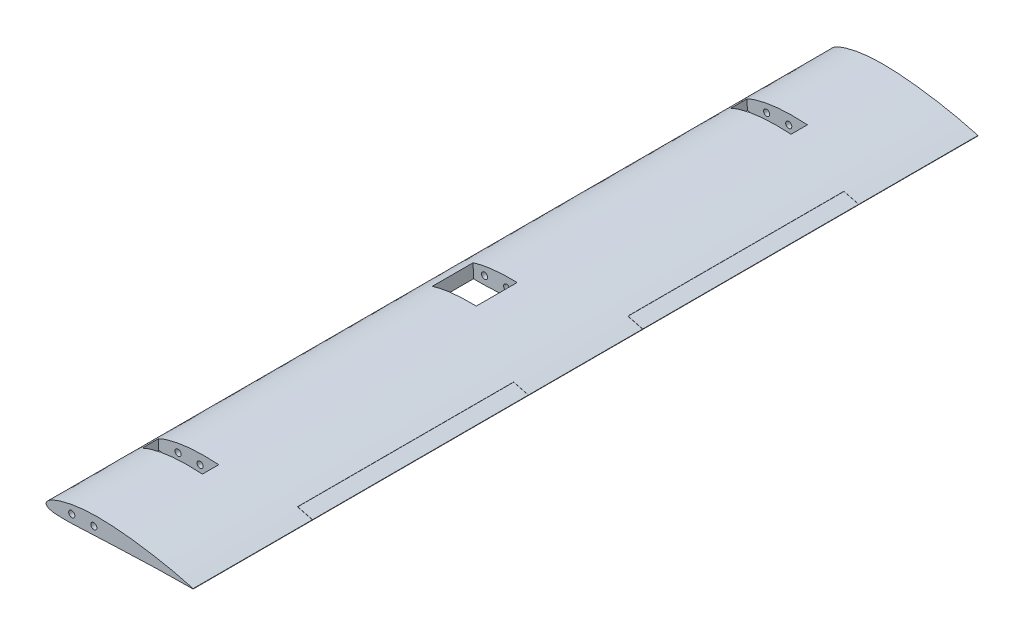
SolidWorks part; units mm, degrees
material "Styrofoam Core 20"
ref_plane "Front Plane" through (0, 0, 0) normal (0, 0, 1) x (1, 0, 0)
ref_plane "Top Plane" through (0, 0, 0) normal (0, 1, 0) x (1, 0, 0)
ref_plane "Right Plane" through (0, 0, 0) normal (1, 0, 0) x (0, 0, -1)
other "Center of Mass"
curve "NACA 4412"
  spline degree 3 poles (25.4, 0.033, 0) (24.9771, 0.1481, 0) (24.1334, 0.3778, 0) (22.4431, 0.7955, 0) (20.3293, 1.2569, 0) (17.7869, 1.7118, 0) (15.2464, 2.0846, 0) (12.7045, 2.3505, 0) (10.1628, 2.5164, 0) (8.041, 2.5181, 0) (6.3469, 2.4009, 0) (5.0745, 2.2465, 0) (3.7995, 2.0188, 0) (2.7428, 1.745, 0) (1.8961, 1.4685, 0) (1.2577, 1.2074, 0) (0.7129, 0.9251, 0) (0.2401, 0.5874, 0) (-0.1715, 0.0442, 0) (0.2727, -0.3711, 0) (0.7261, -0.5342, 0) (1.266, -0.6443, 0) (1.9036, -0.7002, 0) (2.7513, -0.7398, 0) (3.8103, -0.7368, 0) (5.0806, -0.7013, 0) (6.3499, -0.6336, 0) (8.0433, -0.5544, 0) (10.1596, -0.4528, 0) (12.7001, -0.3574, 0) (15.2397, -0.2514, 0) (17.7796, -0.1611, 0) (20.3198, -0.0947, 0) (22.4366, -0.061, 0) (24.13, -0.0388, 0) (24.9767, -0.035, 0) (25.4, -0.033, 0) knots 0 0 0 0 0.025305 0.050488 0.10052 0.150191 0.199587 0.24874 0.297716 0.346601 0.371103 0.395726 0.42057 0.445825 0.458702 0.47192 0.485786 0.493461 0.506863 0.516148 0.522766 0.535269 0.547551 0.559786 0.584229 0.608681 0.633151 0.657622 0.706558 0.755482 0.804406 0.85332 0.902221 0.951113 0.975557 1 1 1 1
sketch "Sketch2" plane through (0, 0, 0) normal (0, 0, 1) x (1, 0, 0)
  line L1 (228.6, 12.387) -> (228.6, 11.7928)
  line L2 (40.005, 31.2493) -> (40.005, 5.6305) construction
  line L3 (68.58, 34.393) -> (68.58, 6.961) construction
  line L4 (74.2832, 19.3375) -> (40.005, 18.4399) construction
  line L5 (0, 0) -> (0, 12.7) construction
  line L6 (40.005, 18.4399) -> (60.8151, 18.4399) construction
  line L7 (68.58, 34.393) -> (228.6056, 20.677) construction
  line L8 (228.6056, 20.677) -> (68.58, 6.961) construction
  line L9 (68.58, 20.677) -> (228.6056, 20.677) construction
  line L11 (59.9523, -93.7228) -> (219.9779, -107.4388)
  line L12 (219.9779, -107.4388) -> (59.9523, -121.1548)
  line L14 (61.264, -169.3292) -> (106.984, -169.3292)
  line L16 (106.984, -141.8972) -> (61.264, -141.8972)
  line L17 (106.984, -141.8972) -> (221.2897, -155.6132)
  line L18 (106.984, -169.3292) -> (221.2897, -155.6132)
  circle A0 centre (40.005, 18.4399) radius 4.7625
  circle A1 centre (74.2832, 19.3375) radius 4.7625
  circle A2 centre (30.4326, -102.8904) radius 4.7625
  circle A3 centre (47.3544, -108.3106) radius 4.7625
  circle A4 centre (31.7443, -151.0648) radius 4.7625
  circle A5 centre (48.6661, -156.485) radius 4.7625
  ellipse E0 centre (68.58, 20.677) end of major axis (0, 20.677) minor radius 13.716 (68.58, 34.393) -> (68.58, 6.961) ccw construction
  ellipse E1 centre (59.9523, -107.4388) end of major axis (128.5323, -107.4388) minor radius 13.716 (59.9523, -93.7228) -> (59.9523, -121.1548) ccw
  ellipse E2 centre (61.264, -155.6132) end of major axis (129.844, -155.6132) minor radius 13.716 (61.264, -141.8972) -> (61.264, -169.3292) ccw
  spline S1 degree 3 poles (228.6, 12.387) (224.795, 13.4228) (217.2034, 15.4895) (201.9951, 19.2471) (182.9766, 23.3988) (160.101, 27.4914) (137.2432, 30.846) (114.3726, 33.2389) (91.504, 34.7313) (72.413, 34.7464) (57.1699, 33.6918) (45.7222, 32.3028) (34.2497, 30.2543) (24.7428, 27.7908) (17.1245, 25.3027) (11.3801, 22.9538) (6.4787, 20.4136) (2.2242, 17.375) (-1.4793, 12.488) (2.5182, 8.7506) (6.5972, 7.2835) (11.455, 6.2932) (17.1921, 5.7898) (24.819, 5.4335) (34.3469, 5.4602) (45.7763, 5.78) (57.1976, 6.389) (72.4334, 7.1015) (91.4748, 8.016) (114.3327, 8.8746) (137.1833, 9.8281) (160.036, 10.6401) (182.8906, 11.2375) (201.9369, 11.5408) (217.1729, 11.7405) (224.791, 11.7754) (228.6, 11.7928) knots 0 0 0 0 0.025305 0.050488 0.10052 0.150191 0.199587 0.24874 0.297716 0.346601 0.371103 0.395726 0.42057 0.445825 0.458702 0.47192 0.485786 0.493461 0.506863 0.516148 0.522766 0.535269 0.547551 0.559786 0.584229 0.608681 0.633151 0.657622 0.706558 0.755482 0.804406 0.85332 0.902221 0.951113 0.975557 1 1 1 1
  point P11 (40.005, 18.4399)
  dimension "D3" = 9.525
  dimension "D4" = 9.525
  dimension "D10" = 9.525
  dimension "D11" = 9.525
  dimension "D12" = 9.525
  dimension "D13" = 9.525
  dimension "D1" = 228.6
  dimension "D5" = 34.29
  dimension "D6" = 12.7
  dimension "D8" = 1.5
  dimension "D9" = 40.005
  dimension "D2" = 68.58
  dimension "D7" = 27.432
  dimension "D14" = 45.72
extrude "Extrude airfoil" add sketch "Sketch2" along normal blind 1219.2 contours S1 A0 | L1 S1 A0 region at (97.363, 19.2157, 0)
sketch "Sketch3" plane through (0, 0, 0) normal (0, 1, 0) x (1, 0, 0)
  line L1 (228.6, -520.7) -> (205.74, -520.7)
  line L4 (205.74, -520.7) -> (205.74, -185.42)
  line L5 (228.6, -185.42) -> (205.74, -185.42)
  line L8 (0, 0) -> (0, -1219.2) construction
  line L9 (0, -609.6) -> (228.6, -609.6) construction
  line L10 (228.6, -1033.78) -> (228.6, -698.5)
  line L15 (228.6, -185.42) -> (228.6, -520.7)
  line L17 (228.6, -1219.2) -> (228.6, 0) construction
  line L18 (228.6, -1033.78) -> (205.74, -1033.78)
  line L19 (205.74, -698.5) -> (205.74, -1033.78)
  line L20 (228.6, -698.5) -> (205.74, -698.5)
  dimension "D1" = 22.86
  dimension "D2" = 335.28
  dimension "D3" = 88.9
extrude "Ailerons" cut sketch "Sketch3" against normal through all and the other way through all thin thin type one direction wall 0.254
ref_plane "Plane1" through (-0.4551, 17.3804, 0) normal (-0.0262, 0.9997, 0) x (0, 0, -1)
sketch "Sketch5" plane through (-0.4551, 17.3804, 0) normal (-0.0262, 0.9997, 0) x (0, 0, -1)
  line L0 (0, 0) -> (-1219.2, 0)
  line L1 (-609.6, 0) -> (-609.6, -227.3868) construction
  line L2 (-609.6, -57.15) -> (-1066.8, -57.15) construction
  line L3 (-139.7, -10.16) -> (-165.1, -104.14) construction
  line L4 (-1079.5, -104.14) -> (-1054.1, -104.14)
  line L5 (-1079.5, -104.14) -> (-1079.5, -10.16)
  line L6 (-1079.5, -10.16) -> (-1054.1, -10.16)
  line L7 (-1054.1, -104.14) -> (-1054.1, -10.16)
  line L8 (-1079.5, -104.14) -> (-1054.1, -10.16) construction
  line L9 (-1079.5, -10.16) -> (-1054.1, -104.14) construction
  line L10 (-139.7, -104.14) -> (-165.1, -10.16) construction
  line L11 (-165.1, -104.14) -> (-165.1, -10.16)
  line L12 (-139.7, -104.14) -> (-139.7, -10.16)
  line L13 (-139.7, -104.14) -> (-165.1, -104.14)
  line L14 (-139.7, -10.16) -> (-165.1, -10.16)
  line L16 (-577.85, -91.44) -> (-641.35, -91.44)
  line L17 (-577.85, -91.44) -> (-577.85, -22.86)
  line L18 (-577.85, -22.86) -> (-641.35, -22.86)
  line L19 (-641.35, -91.44) -> (-641.35, -22.86)
  point P19 (-609.6, -22.86)
  dimension "D1" = 1219.2
  dimension "D2" = 57.15
  dimension "D4" = 93.98
  dimension "D5" = 457.2
  dimension "D6" = 22.86
  dimension "D7" = 91.44
  dimension "D8" = 31.75
extrude "Cut-Extrude1" cut sketch "Sketch5" against normal through all and the other way through all contours L12 L14 L11 L13 | L7 L6 L5 L4 | L18 L19 L16 L17
equation "\"D1@Extrude airfoil\"=\"span\""
equation "\"D1@Sketch2\"= \"wing_chord\""
equation "\"D1@Sketch3\"=\"wing_chord\"*0.1"
equation "\"D2@Sketch3\"=\"span\"/2*0.55"
equation "\"D3@Sketch2\"=\"wing_spar_d\""
equation "\"D4@Sketch2\"=\"wing_spar_d\""
equation "\"D8@Sketch2\"=\"wing_angle\""
equation "\"D1@Sketch5\"=\"span\""
equation "\"D2@Sketch5\"=\"x_cg_from_le\""
equation "\"D3@Sketch5\"=\"boom_mount_l\""
equation "\"D5@Sketch5\"=\"wing_mount_y\"/2"
equation "\"D5@Sketch2\"= \"wing_spar_spacing\""
equation "\"D9@Sketch2\"= \"x_cg_from_le\" - \"wing_spar_spacing\"/2"
equation "\"D6@Sketch5\"= \"x_cg_from_le\" - \"wing_spar_spacing\""
equation "\"D7@Sketch5\"= \"wing_chord\"*0.4"
equation "\"D8@Sketch5\"= \"wing_mount_l\"/2"
equation "\"span\"= 48"
equation "\"wing_chord\"= 9"
equation "\"fuse_len\"= 15"
equation "\"fuse_height\"= 5"
equation "\"fuse_wid\"= 5"
equation "\"foam_t\"= 0.1875"
equation "\"main_spar_len\"= 36"
equation "\"x_fuse_to_wing\"= 3"
equation "\"x_cg_from_le\"= 2.25"
equation "\"boom_len\"= 30"
equation "\"wing_angle\"= 1.5"
equation "\"boom_d\"= 0.75"
equation "\"wing_spar_d\"= 0.375"
equation "\"wing_spar_l\"= 48"
equation "\"wing_spar_spacing\"= 1.35"
equation "\"wing_mount_l\"= 2.5"
equation "\"boom_mount_l\"= 1"
equation "\"vstab_span\"= 6.5"
equation "\"hstab_span\"= 15.25"
equation "\"tail_chord\"= 5"
equation "\"wing_spar_ID\"= 0.25"
equation "\"fuse_inner_arc_length\" = 0.5"
equation "\"fuse_inner_r\" = \"fuse_inner_arc_length\" * 4 / (2*pi)"
equation "\"fuse_outer_r\" = \"fuse_inner_r\" + \"foam_t\""
equation "\"wing_mount_bolt_spacing\" = \"wing_mount_l\" * 0.5"
equation "\"fuse_inner_h\" = \"fuse_height\" - 2 * \"foam_t\""
equation "\"fuse_inner_w\" = \"fuse_wid\" - 2 * \"fuse_outer_r\""
equation "\"wing_mount_y\" = 36"
equation "\"D2@Sketch2\"=\"wing_chord\"*0.3"
equation "\"D7@Sketch2\"=\"wing_chord\"*0.12"
equation "\"D14@Sketch2\"=\"wing_chord\"*0.2"
